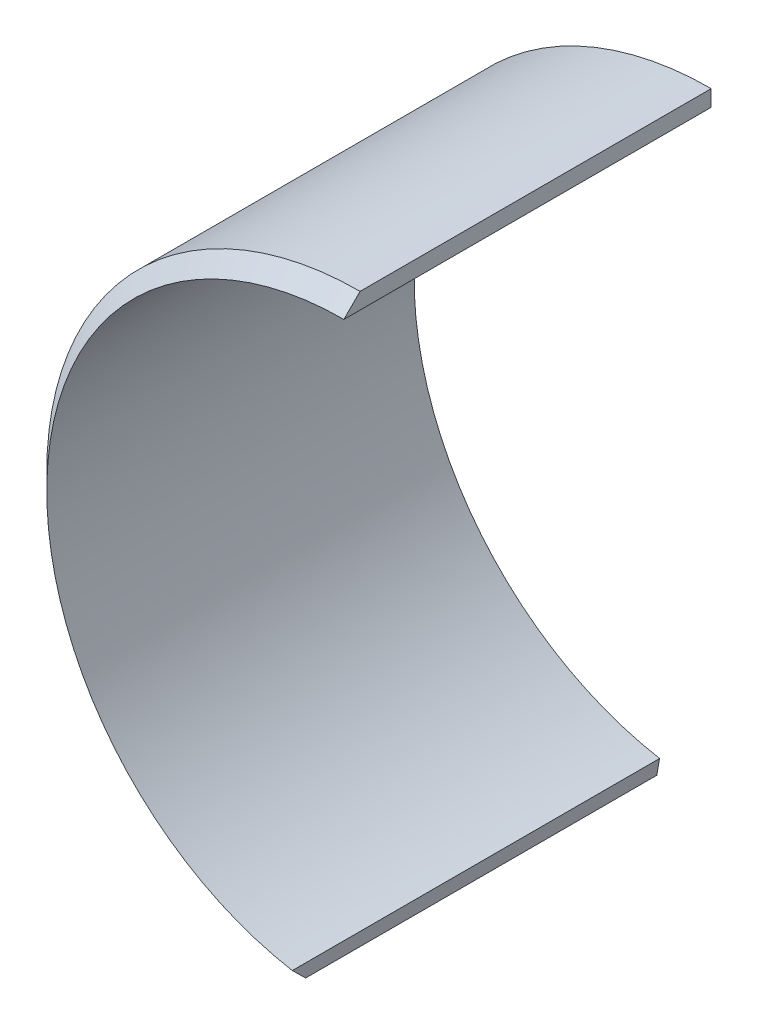
SolidWorks part; units mm, degrees
ref_plane "Front Plane" through (0, 0, 0) normal (0, 0, 1) x (1, 0, 0)
ref_plane "Top Plane" through (0, 0, 0) normal (0, 1, 0) x (1, 0, 0)
ref_plane "Right Plane" through (0, 0, 0) normal (1, 0, 0) x (0, 0, -1)
sketch "Sketch1" plane through (0, 0, 0) normal (0, 0, 1) x (1, 0, 0)
  line L0 (-2.5582, -14.5082) -> (-2.4259, -13.7578)
  line L1 (0, 13.97) -> (0, 14.732)
  arc A0 (0, 13.97) -> (-2.4259, -13.7578) centre (0, 0) ccw
  arc A1 (0, 14.732) -> (-2.5582, -14.5082) centre (0, 0) ccw
  dimension "D1" = 27.94
  dimension "D2" = 0.762
  dimension "D3" = 170
extrude "Boss-Extrude1" add sketch "Sketch1" along normal blind 19.05
chamfer "Chamfer1" distance 2.54 angle 45 1 edges at (-14.6759, 1.284, 19.05)
